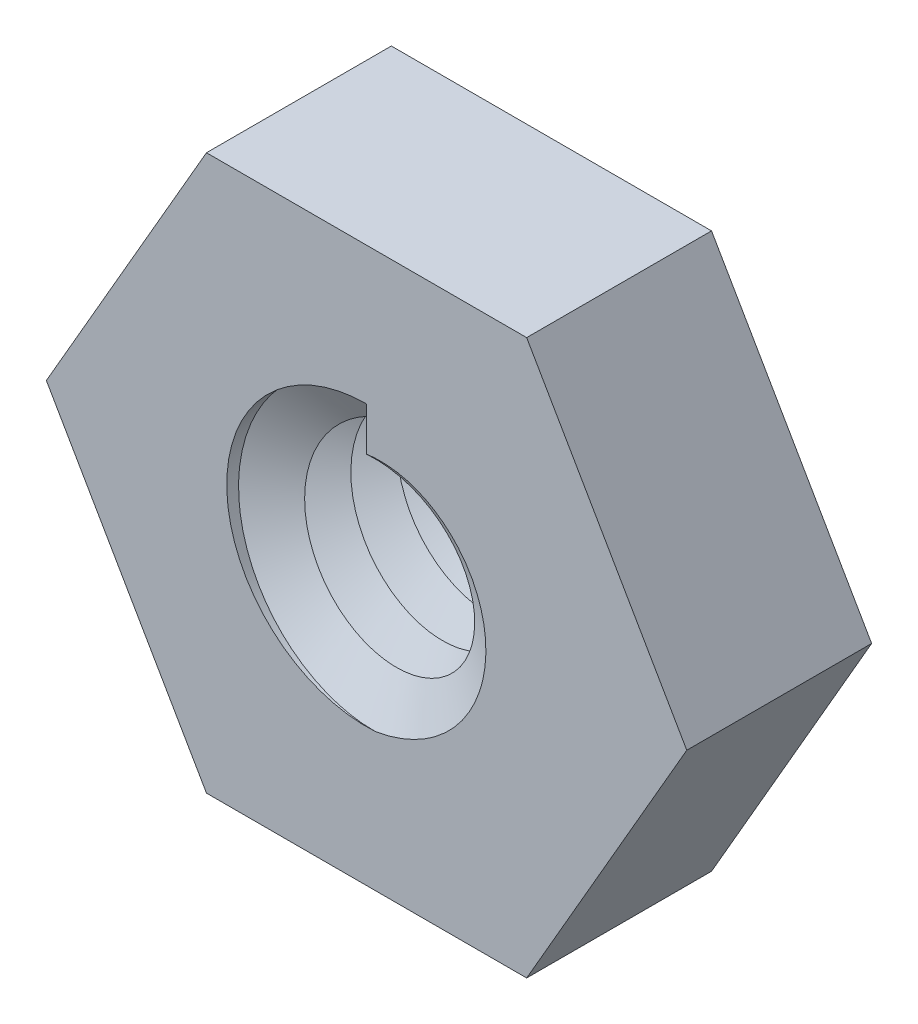
SolidWorks part; units mm, degrees
ref_plane "Plano frontal" through (0, 0, 0) normal (0, 0, 1) x (1, 0, 0)
ref_plane "Plano superior" through (0, 0, 0) normal (0, 1, 0) x (1, 0, 0)
ref_plane "Plano direito" through (0, 0, 0) normal (1, 0, 0) x (0, 0, -1)
sketch "Esboço1" plane through (0, 0, 0) normal (0, 0, 1) x (1, 0, 0)
  line L1 (-13.8564, 0) -> (-6.9282, -12)
  line L2 (-6.9282, -12) -> (6.9282, -12)
  line L3 (6.9282, -12) -> (13.8564, 0)
  line L4 (13.8564, 0) -> (6.9282, 12)
  line L5 (6.9282, 12) -> (-6.9282, 12)
  line L6 (-6.9282, 12) -> (-13.8564, 0)
  circle A0 centre (0, 0) radius 12 construction
  circle A1 centre (0, 0) radius 6.05
  dimension "D1" = 24
  dimension "D2" = 12.1
extrude "Ressalto-extrusão1" add sketch "Esboço1" along normal blind 8
sketch "Esboço2" plane through (0, 0, 8) normal (0, 0, 1) x (1, 0, 0)
  circle A0 centre (0, 0) radius 6.05
curve "Hélice/Espiral1" pitch 2 height 10.5 radius 6.05 centre (0, 0, 8) axis (0, 0, -1) start towards (0, 1, 0)
sketch "Esboço3" plane through (0, 0, 0) normal (0, 1, 0) x (1, 0, 0)
  line L0 (6.05, 2.5) -> (6.05, 1.52)
  line L1 (6.05, 1.52) -> (4.1674, 2.5)
  line L2 (4.1674, 2.5) -> (6.05, 3.48)
  line L3 (6.05, 3.48) -> (6.05, 2.5)
  spline S0 degree 3 poles (0, -8) (0.7869, -7.9586) (2.3778, -7.8749) (4.3888, -7.75) (5.7352, -7.625) (6.2075, -7.5) (5.735, -7.375) (4.3894, -7.25) (2.3755, -7.125) (0, -7) (-2.3755, -6.875) (-4.3894, -6.75) (-5.735, -6.625) (-6.2075, -6.5) (-5.735, -6.375) (-4.3894, -6.25) (-2.3755, -6.125) (0, -6) (2.3755, -5.875) (4.3894, -5.75) (5.735, -5.625) (6.2075, -5.5) (5.735, -5.375) (4.3894, -5.25) (2.3755, -5.125) (0, -5) (-2.3755, -4.875) (-4.3894, -4.75) (-5.735, -4.625) (-6.2075, -4.5) (-5.735, -4.375) (-4.3894, -4.25) (-2.3755, -4.125) (0, -4) (2.3755, -3.875) (4.3894, -3.75) (5.735, -3.625) (6.2075, -3.5) (5.735, -3.375) (4.3894, -3.25) (2.3755, -3.125) (0, -3) (-2.3755, -2.875) (-4.3894, -2.75) (-5.735, -2.625) (-6.2075, -2.5) (-5.735, -2.375) (-4.3894, -2.25) (-2.3755, -2.125) (0, -2) (2.3755, -1.875) (4.3894, -1.75) (5.735, -1.625) (6.2075, -1.5) (5.735, -1.375) (4.3894, -1.25) (2.3755, -1.125) (0, -1) (-2.3755, -0.875) (-4.3894, -0.75) (-5.735, -0.625) (-6.2075, -0.5) (-5.735, -0.375) (-4.3894, -0.25) (-2.3755, -0.125) (0, 0) (2.3755, 0.125) (4.3894, 0.25) (5.735, 0.375) (6.2075, 0.5) (5.735, 0.625) (4.3894, 0.75) (2.3755, 0.875) (0, 1) (-2.3755, 1.125) (-4.3894, 1.25) (-5.735, 1.375) (-6.2075, 1.5) (-5.735, 1.625) (-4.3894, 1.75) (-2.3755, 1.875) (0, 2) (2.3755, 2.125) (4.3894, 2.25) (5.735, 2.3749) (6.05, 2.4586) (6.05, 2.5) knots 0 0 0 0 0.011905 0.02381 0.035714 0.047619 0.059524 0.071429 0.083333 0.095238 0.107143 0.119048 0.130952 0.142857 0.154762 0.166667 0.178571 0.190476 0.202381 0.214286 0.22619 0.238095 0.25 0.261905 0.27381 0.285714 0.297619 0.309524 0.321429 0.333333 0.345238 0.357143 0.369048 0.380952 0.392857 0.404762 0.416667 0.428571 0.440476 0.452381 0.464286 0.47619 0.488095 0.5 0.511905 0.52381 0.535714 0.547619 0.559524 0.571429 0.583333 0.595238 0.607143 0.619048 0.630952 0.642857 0.654762 0.666667 0.678571 0.690476 0.702381 0.714286 0.72619 0.738095 0.75 0.761905 0.77381 0.785714 0.797619 0.809524 0.821429 0.833333 0.845238 0.857143 0.869048 0.880952 0.892857 0.904762 0.916667 0.928571 0.940476 0.952381 0.964286 0.97619 0.988095 1 1 1 1 construction
  dimension "D1" = 0.98
  dimension "D2" = 0.98
  dimension "D3" = 55
sweep "Varredura1" add profiles "Esboço3" path "Hélice/Espiral1"
sketch "Esboço4" plane through (0, -12, 0) normal (0, -1, 0) x (1, 0, 0)
  line L1 (-6.9282, 8) -> (10.494, 8)
  line L2 (-6.9282, 8) -> (-6.9282, 13.3562)
  line L3 (-6.9282, 13.3562) -> (10.494, 13.3562)
  line L4 (10.494, 8) -> (10.494, 13.3562)
  line L5 (6.9282, 0) -> (-9.723, 0)
  line L6 (6.9282, 0) -> (6.9282, -9.0024)
  line L7 (6.9282, -9.0024) -> (-9.723, -9.0024)
  line L8 (-9.723, 0) -> (-9.723, -9.0024)
extrude "Corte-extrusão1" cut sketch "Esboço4" against normal blind 25
